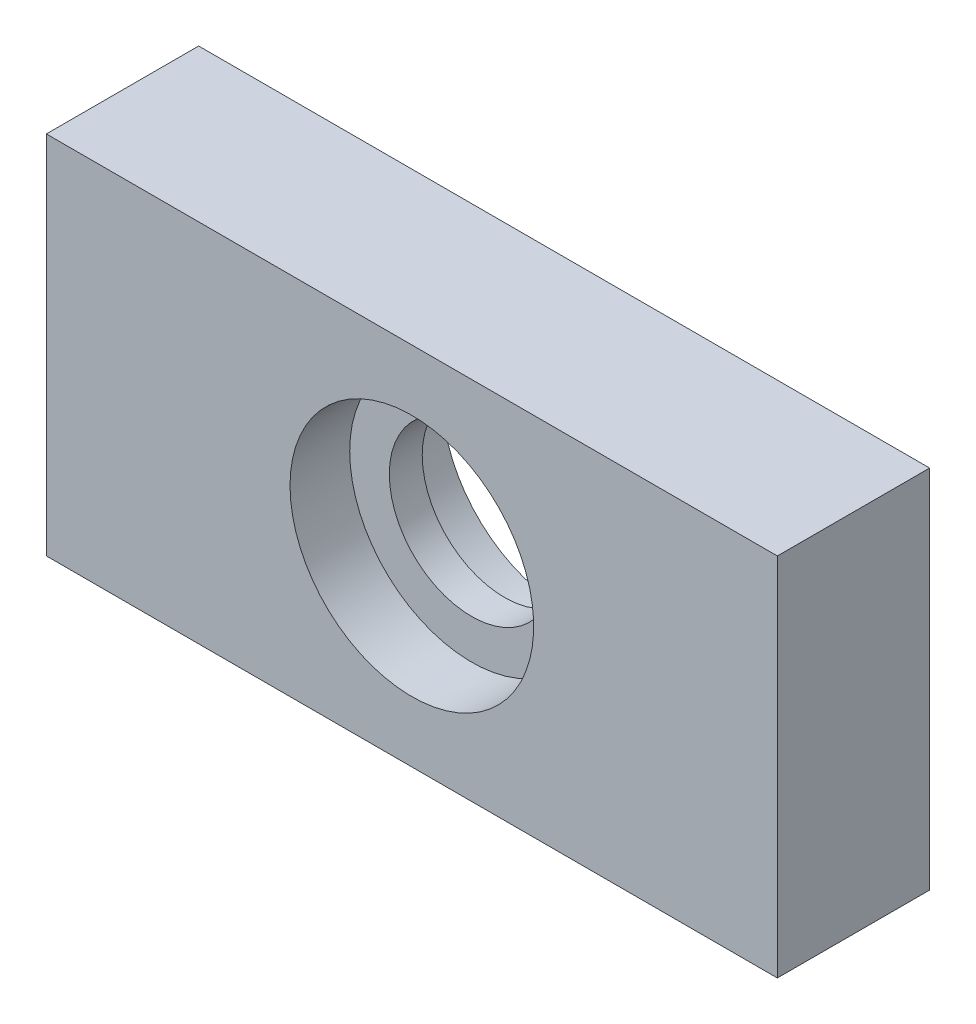
SolidWorks part; units mm, degrees
ref_plane "Front Plane" through (0, 0, 0) normal (0, 0, 1) x (1, 0, 0)
ref_plane "Top Plane" through (0, 0, 0) normal (0, 1, 0) x (1, 0, 0)
ref_plane "Right Plane" through (0, 0, 0) normal (1, 0, 0) x (0, 0, -1)
sketch "Sketch1" plane through (0, 0, 0) normal (0, 0, 1) x (1, 0, 0)
  line L1 (0, 0) -> (152.4, 0)
  line L2 (0, 0) -> (0, 76.2)
  line L3 (0, 76.2) -> (152.4, 76.2)
  line L4 (152.4, 0) -> (152.4, 76.2)
  dimension "D1" = 152.4
  dimension "D2" = 76.2
extrude "Boss-Extrude1" add sketch "Sketch1" along normal blind 31.75
sketch "Sketch2" plane through (0, 0, 0) normal (0, 0, -1) x (-1, 0, 0)
  line L0 (0, 38.1) -> (-152.4, 38.1) construction
  line L1 (0, 76.2) -> (0, 0) construction
  line L2 (-152.4, 0) -> (-152.4, 76.2) construction
  line L4 (-152.4, 76.2) -> (0, 76.2) construction
  line L5 (-76.2, 76.2) -> (-76.2, 0) construction
  line L6 (0, 0) -> (-152.4, 0) construction
  circle A0 centre (-76.2, 38.1) radius 25.4
  circle A1 centre (-76.2, 38.1) radius 17.145
  dimension "D1" = 50.8
  dimension "D2" = 34.29
extrude "Cut-Extrude1" cut sketch "Sketch2" against normal through all contours A1
extrude "Cut-Extrude3" cut sketch "Sketch2<2>" against normal blind 12.446
sketch "Sketch2<2>" plane through (0, 0, 0) normal (0, 0, -1) x (-1, 0, 0) same geometry as "Sketch2"
ref_plane "Plane2" through (0, 0, 15.875) normal (0, 0, -1) x (-1, 0, 0)
mirror "Mirror2" about plane through (0, 0, 15.875) normal (0, 0, -1) of "Cut-Extrude3"
equation "\"through_diamiter\"= 1.35"
equation "\"D2@Sketch2\"=\"through_diamiter\""
equation "\"bearing depth\"= 0.5"
